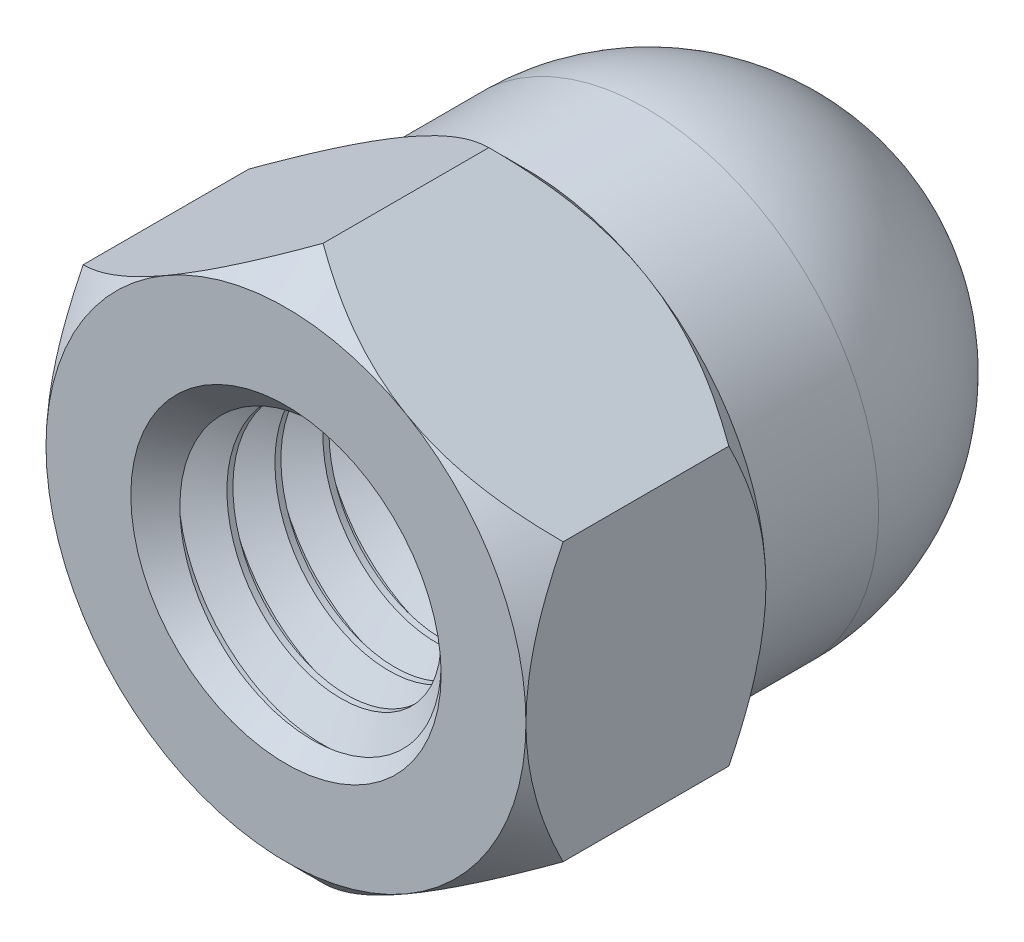
SolidWorks part; units mm, degrees
ref_plane "Front Plane" through (0, 0, 0) normal (0, 0, 1) x (1, 0, 0)
ref_plane "Top Plane" through (0, 0, 0) normal (0, 1, 0) x (1, 0, 0)
ref_plane "Right Plane" through (0, 0, 0) normal (1, 0, 0) x (0, 0, -1)
sketch "Sketch1" plane through (0, 0, 0) normal (-1, 0, 0) x (0, 0, 1)
  line L0 (-5, 0) -> (5, 0) construction
  line L1 (-5, 0) -> (-5, 4) construction
  line L2 (5, 4) -> (-5, 4) construction
  line L3 (5, 2.5) -> (-2.21, 2.5) construction
  line L4 (5, 0) -> (5, 4) construction
  line L5 (-2.21, 2.5) -> (-2.21, 0) construction
  line L7 (-2.21, 2.5) -> (-2.8799, 0) construction
  line L8 (5.75, 2.5866) -> (5.35, 1.8938) construction
  line L9 (5.35, 1.8938) -> (4.95, 2.5866) construction
  line L10 (4.95, 2.5866) -> (5.75, 2.5866) construction
  line L11 (5.35, 1.8938) -> (5.35, 1.9804) construction
  line L12 (5.35, 2.5866) -> (5.35, 2.5) construction
  line L13 (5.7, 2.5) -> (5, 2.5) construction
  line L14 (5.3, 1.9804) -> (5.4, 1.9804) construction
  line L15 (5.35, 2.5433) -> (4.975, 2.5433) construction
  line L16 (5.35, 2.5433) -> (5.725, 2.5433) construction
  arc A2 (-5, 0) -> (-1, 4) centre (-1, 0) cw construction
  point P3 (0, 0)
  point P23 (1, 4)
  dimension "Height" = 10
  dimension "Width" = 8
  dimension "Thread Depth" = 7.21
  dimension "Thread OD" = 5
  dimension "Thread Tip Angle" = 75
  dimension "Thread Pitch" = 0.8
  dimension "D1" = 0.1
  dimension "Hex Thickness (m)" = 4
ref_plane "Plane1" through (0, 0, 5) normal (0, 0, 1) x (1, 0, 0)
ref_plane "Plane2" through (0, 0, 1) normal (0, 0, 1) x (1, 0, 0)
ref_plane "Plane3" through (0, 0, -2.21) normal (0, 0, 1) x (1, 0, 0)
sketch "Sketch7" plane through (0, 0, 5) normal (0, 0, 1) x (1, 0, 0)
  line L1 (0, 4.6188) -> (-4, 2.3094)
  line L2 (-4, 2.3094) -> (-4, -2.3094)
  line L3 (-4, -2.3094) -> (0, -4.6188)
  line L4 (0, -4.6188) -> (4, -2.3094)
  line L5 (4, -2.3094) -> (4, 2.3094)
  line L6 (4, 2.3094) -> (0, 4.6188)
  circle A0 centre (0, 0) radius 4 construction
  point P0 (0, 4)
extrude "Boss-Extrude2" add sketch "Sketch7" against normal up to vertex (4 mm away) up to point (0, 4, 1)
sketch "Sketch8" plane through (0, 0, 5) normal (0, 0, 1) x (1, 0, 0)
  circle A0 centre (0, 0) radius 4
extrude "Cut-Extrude3" cut sketch "Sketch8" against normal through all draft 45 flip side to cut
sketch "Sketch9" plane through (0, 0, 1) normal (0, 0, 1) x (1, 0, 0)
  circle A1 centre (0, 0) radius 4
  circle A2 centre (0, 0) radius 4
  dimension "D1" = 0
extrude "Cut-Extrude4" cut sketch "Sketch9" along normal through all draft 45 flip side to cut
sketch "Sketch10" plane through (0, 0, 0) normal (1, 0, 0) x (0, 0, -1)
  line L0 (1, 4) -> (-1, 4)
  line L1 (5, 0) -> (-5, 0) construction
  line L3 (5, 0) -> (-1, 0)
  line L4 (-1, 4) -> (-1, 0)
  arc A0 (5, 0) -> (1, 4) centre (1, 0) ccw construction
  arc A4 (5, 0) -> (1, 4) centre (1, 0) ccw
revolve "Revolve1" add sketch "Sketch10" angle 360 about L0
sketch "Sketch16" plane through (0, 0, 0) normal (0, 0, 1) x (1, 0, 0)
  line L0 (0, 0) -> (0, -2.5) construction
  line L1 (0, 0) -> (0.9567, -2.3097) construction
  circle A0 centre (0, 0) radius 2.5 construction
  point P3 (0.9567, -2.3097)
  dimension "D1" = 22.5
sketch "Sketch17" plane through (0, 0, 0) normal (1, 0, 0) x (0, 0, -1)
  line L0 (2.21, 2.5) -> (2.8799, 0) construction
  line L1 (-5, 2.5) -> (2.21, 2.5) construction
  line L2 (2.21, 2.5) -> (2.8799, 0)
  line L3 (-5, 2.5) -> (2.21, 2.5)
  line L4 (2.8799, 0) -> (2.21, -2.5)
  line L5 (2.21, -2.5) -> (-5, -2.5)
sketch "Sketch11" plane through (0, 0, 0) normal (1, 0, 0) x (0, 0, -1)
  line L2 (-5, 0) -> (-5, 4) construction
  line L3 (-5, 2.5) -> (2.21, 2.5) construction
  line L6 (-5, 0) -> (-5, 2.5)
  line L7 (-5, 2.5) -> (2.21, 2.5)
  line L8 (2.21, 2.5) -> (2.8799, 0) construction
  line L9 (2.21, 2.5) -> (2.8799, 0)
  line L10 (5, 0) -> (-5, 0) construction
  line L11 (2.8799, 0) -> (-5, 0)
revolve "Cut-Revolve1" cut sketch "Sketch11" angle 360 about L0
sketch "Sketch12" plane through (0, 0, 5) normal (0, 0, 1) x (1, 0, 0)
  circle A0 centre (0, 0) radius 2.5
  point P0 (0, 2.5)
curve "Helix/Spiral1" pitch 0.8 height 8.01 turns 10.0125
sketch "Sketch13" plane through (0, 0, 0) normal (1, 0, 0) x (0, 0, -1)
  line L0 (-5.725, 2.5433) -> (-5.4, 1.9804)
  line L1 (-5.4, 1.9804) -> (-5.3, 1.9804)
  line L2 (-5.3, 1.9804) -> (-4.975, 2.5433)
  line L3 (-4.975, 2.5433) -> (-5.725, 2.5433)
sweep "Sweep1" add profiles "Sketch13" path "Helix/Spiral1"
sketch "Sketch14" plane through (0, 0, 0) normal (1, 0, 0) x (0, 0, -1)
  line L0 (5, 0) -> (5, 4) construction
  line L1 (1, 3.8796) -> (-1, 3.8796)
  line L2 (5, 1.25) -> (5, 4) construction
  line L4 (5, 1.25) -> (4.7592, 1.25) construction
  line L5 (2.21, 2.5) -> (2.21, 0) construction
  line L7 (5.2408, 4) -> (5.2408, 1.25)
  line L8 (5.2408, 1.25) -> (5, 1.25) construction
  line L10 (5.2408, 1.25) -> (5.2408, 0)
  line L12 (5.2408, 0) -> (5, 0)
  line L13 (5, 0) -> (-5, 0) construction
  line L14 (5, 4) -> (1, 4)
  line L15 (5, 4) -> (5.2408, 4)
  line L17 (1, 4) -> (1, 3.7592) construction
  line L21 (5, 0) -> (5, -2.8136) construction
  line L22 (-5, 4) -> (5, 4) construction
  line L23 (-1, 4) -> (-1, 3.4641) construction
  line L24 (1, 4) -> (-1, 4)
  line L25 (-1, 4) -> (-1, 3.8796)
  line L26 (1, 4) -> (1, -4) construction
  arc A0 (5, 0) -> (1, 3.8796) centre (1, -0.1222) ccw
  point P9 (2.21, 1.25)
revolve "Cut-Revolve4" cut sketch "Sketch14" angle 360 about L0
sketch "Sketch15" plane through (0, 0, 5) normal (0, 0, 1) x (1, 0, 0)
  circle A0 centre (0, 0) radius 2.5866
extrude "Cut-Extrude5" cut sketch "Sketch15" against normal through all draft 45 and the other way through all draft 45
equation "\"D1@Sketch1\" = \"Thread Pitch@Sketch1\" / 8"
equation "\"D3@Helix/Spiral1\" = \"Thread Depth@Sketch1\" + \"Thread Pitch@Sketch1\""
equation "\"D4@Helix/Spiral1\" = \"Thread Pitch@Sketch1\""
